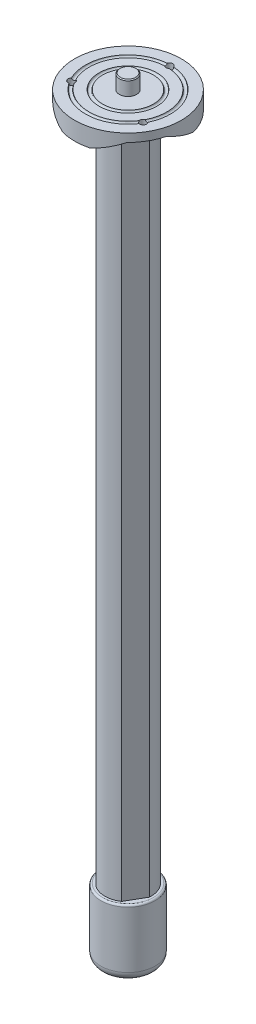
SolidWorks part; units mm, degrees
ref_plane "Front Plane" through (0, 0, 0) normal (0, 0, 1) x (1, 0, 0)
ref_plane "Top Plane" through (0, 0, 0) normal (0, 1, 0) x (1, 0, 0)
ref_plane "Right Plane" through (0, 0, 0) normal (1, 0, 0) x (0, 0, -1)
sketch "Sketch2" plane through (0, 0, 0) normal (0, 1, 0) x (1, 0, 0)
  line L0 (-5.6461, 11.6544) -> (5.6461, 11.6544) construction
  line L1 (12.916, -0.9375) -> (7.2699, -10.7168) construction
  line L2 (-5.6, 11.4544) -> (5.6, 11.4544)
  line L3 (12.7198, -0.8774) -> (7.1198, -10.5769)
  line L4 (-7.1198, -10.5769) -> (-12.7198, -0.8774)
  line L5 (-7.2699, -10.7168) -> (-12.916, -0.9375) construction
  arc A0 (-5.6, 11.4544) -> (-12.7198, -0.8774) centre (0, 0) ccw
  arc A1 (-7.1198, -10.5769) -> (7.1198, -10.5769) centre (0, 0) ccw
  arc A2 (12.7198, -0.8774) -> (5.6, 11.4544) centre (0, 0) ccw
  arc A3 (12.916, -0.9375) -> (5.6461, 11.6544) centre (0, 0) ccw construction
  arc A4 (-7.2699, -10.7168) -> (7.2699, -10.7168) centre (0, 0) ccw construction
  arc A5 (-5.6461, 11.6544) -> (-12.916, -0.9375) centre (0, 0) ccw construction
  dimension "D1" = 0.2
extrude "Extrude1" add sketch "Sketch2" along normal mid plane 370
sketch "Sketch3" plane through (0, 185, 0) normal (0, 1, 0) x (1, 0, 0)
  circle A0 centre (0, 0) radius 29.5
  dimension "D1" = 59
extrude "Extrude2" add sketch "Sketch3" along normal blind 10 separate body
ref_plane "Plane1" through (0, 0, -35) normal (0, 0, 1) x (1, 0, 0)
sketch "Sketch7" plane through (0, 0, 0) normal (0, 0, 1) x (1, 0, 0)
  line L0 (0, 203.8228) -> (0, 175.1069) construction
  line L1 (29.5, 195) -> (-29.5, 195) construction
  circle A0 centre (15, 195) radius 1
  circle A1 centre (22.5, 195) radius 1
  dimension "D1" = 30
  dimension "D2" = 45
  dimension "D3" = 2
revolve "Cut-Revolve1" cut sketch "Sketch7" angle 360 about L0
sketch "Sketch6" plane through (0, 185, 0) normal (0, -1, 0) x (1, 0, 0)
  circle A2 centre (0, 0) radius 25.5
  circle A3 centre (0, 0) radius 25.5
  circle A4 centre (0, 0) radius 29.5
  circle A5 centre (0, 0) radius 29.5
  dimension "D1" = 4
  dimension "D2" = 0
extrude "Extrude4" cut sketch "Sketch6" against normal blind 5.5 flip side to cut
sketch "Sketch4" plane through (0, 0, -35) normal (0, 0, 1) x (1, 0, 0)
  line L0 (0, 203.7466) -> (0, 160.4159) construction
  line L1 (8, 190.5) -> (-8, 190.5)
  line L2 (-8, 190.5) -> (-21, 185)
  line L3 (-29.5, 185) -> (29.5, 185) construction
  line L4 (29.5, 195) -> (-29.5, 195) construction
  line L5 (-21, 185) -> (21, 185)
  line L6 (8, 190.5) -> (21, 185)
  point P12 (0, 185)
  point P13 (0, 190.5)
  dimension "D1" = 16
  dimension "D2" = 4.5
  dimension "D3" = 42
  dimension "D4" = 5.5
extrude "Extrude3" cut sketch "Sketch4" along normal blind 23
pattern_circular "CirPattern1" count 3 over 360 about axis through (0, 195, 0) along (0, -1, 0) of "Extrude3"
sketch "Sketch8" plane through (0, 195, 0) normal (0, 1, 0) x (1, 0, 0)
  circle A0 centre (0, 0) radius 4.7625
  dimension "D1" = 9.525
extrude "Extrude5" add sketch "Sketch8" along normal blind 8 separate body
chamfer "Chamfer1" distance 0.5 angle 45 1 edges at (0, 203, 4.7625)
sketch "Sketch9" plane through (0, 185, 0) normal (0, 1, 0) x (1, 0, 0)
  line L3 (-12.7198, -0.8774) -> (-7.1198, -10.5769)
  line L4 (7.1198, -10.5769) -> (12.7198, -0.8774)
  line L5 (5.6, 11.4544) -> (-5.6, 11.4544)
  line L6 (-12.7198, -0.8774) -> (-7.1198, -10.5769)
  line L7 (7.1198, -10.5769) -> (12.7198, -0.8774)
  line L8 (5.6, 11.4544) -> (-5.6, 11.4544)
  arc A3 (-5.6, 11.4544) -> (-12.7198, -0.8774) centre (0, 0) ccw
  arc A4 (-7.1198, -10.5769) -> (7.1198, -10.5769) centre (0, 0) ccw
  arc A5 (12.7198, -0.8774) -> (5.6, 11.4544) centre (0, 0) ccw
  arc A6 (-5.6, 11.4544) -> (-12.7198, -0.8774) centre (0, 0) ccw
  arc A7 (-7.1198, -10.5769) -> (7.1198, -10.5769) centre (0, 0) ccw
  arc A8 (12.7198, -0.8774) -> (5.6, 11.4544) centre (0, 0) ccw
  dimension "D1" = 0
extrude "Extrude6" add sketch "Sketch9" along normal blind 8 separate body
sketch "Sketch10" plane through (0, 0, 0) normal (0, 0, 1) x (1, 0, 0)
  line L0 (0, -169.776) -> (0, -233.5826) construction
  line L1 (15, -185) -> (15, -220)
  line L2 (-7.1198, -185) -> (7.1198, -185) construction
  line L3 (0, -185) -> (15, -185)
  line L4 (-8.9046, -225) -> (11.9553, -225) construction
  line L5 (0, -185) -> (0, -225)
  arc A0 (0, -225) -> (15, -220) centre (0, -200) ccw
  dimension "D1" = 35
  dimension "D2" = 30
  dimension "D3" = 40
revolve "Revolve1" add sketch "Sketch10" angle 360 about L5
fillet "Fillet1" radius 5 1 edges at (-15, -220, 0)
fillet "Fillet2" radius 1 1 edges at (-15, -185, 0)
combine bodies "Combine1" operation type add bodies to combine 111 101
hole_wizard "#10-24 Tapped Hole1" positions "Sketch11" profile "Sketch13" tap size "#10-24" standard "ANSI Inch" end condition through all
sketch "Sketch11" plane through (0, 195, 0) normal (0, 1, 0) x (1, 0, 0)
  line L0 (0, 22.86) -> (19.7973, -11.43) construction
  line L1 (19.7973, -11.43) -> (-19.7973, -11.43) construction
  line L2 (-19.7973, -11.43) -> (0, 22.86) construction
  line L4 (-19.7973, -11.43) -> (0, 0) construction
  line L6 (19.7973, -11.43) -> (0, 0) construction
  line L8 (0, 22.86) -> (0, 0) construction
  circle A0 centre (0, 0) radius 4.2625 construction
  point P1 (0, 22.86)
  point P2 (19.7973, -11.43)
  point P4 (-19.7973, -11.43)
  dimension "D1" = 22.86
sketch "Sketch13" plane through (0, 195, -22.86) normal (1, 0, 0) x (0, 0, 1)
  line L0 (0, 0) -> (0, 420)
  line L1 (0, 420) -> (1.8986, 420)
  line L2 (1.8986, 420) -> (1.8986, 0)
  line L5 (1.8986, 0) -> (0, 0)
  line L11 (0, -6.35) -> (0, 107.95) construction
  dimension "Thread Major Dia." = 3.7973
  dimension "Thru Tap Drill Depth" = 420
